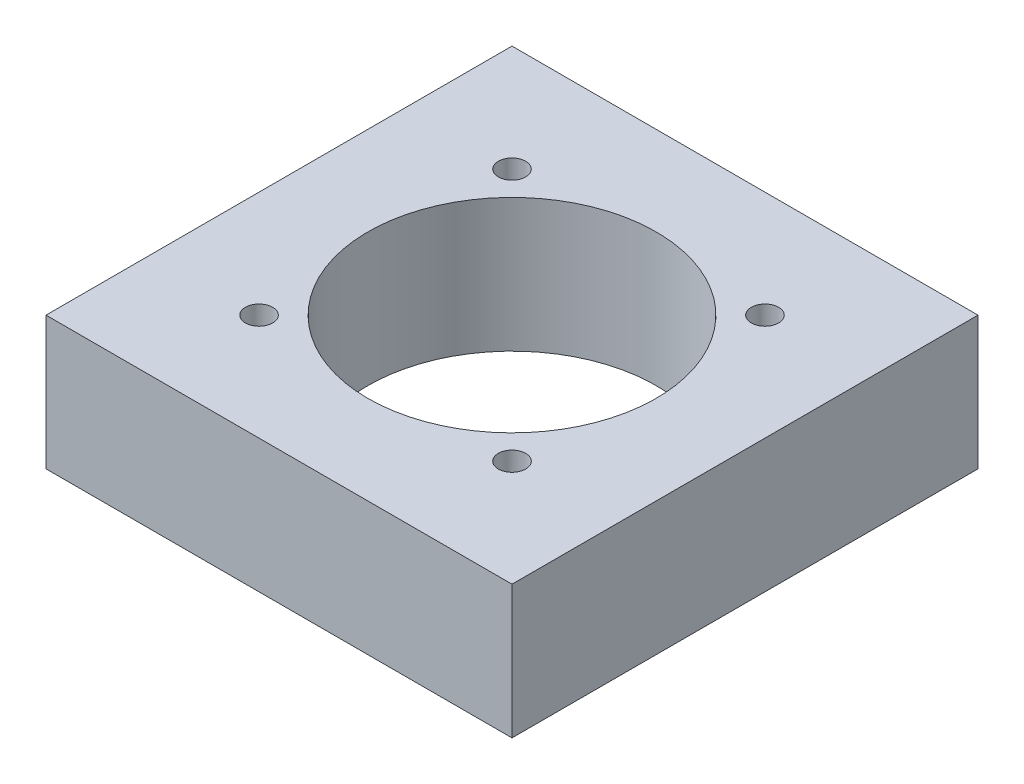
SolidWorks part; units mm, degrees
ref_plane "Front" through (0, 0, 0) normal (0, 0, 1) x (1, 0, 0)
ref_plane "Top" through (0, 0, 0) normal (0, 1, 0) x (1, 0, 0)
ref_plane "Right" through (0, 0, 0) normal (1, 0, 0) x (0, 0, -1)
sketch "Sketch2" plane through (0, 0, 0) normal (0, 1, 0) x (1, 0, 0)
  line L1 (-35, -35) -> (35, -35)
  line L2 (-35, -35) -> (-35, 35)
  line L3 (-35, 35) -> (35, 35)
  line L4 (35, -35) -> (35, 35)
  line L5 (-35, -35) -> (35, 35) construction
  line L6 (-35, 35) -> (35, -35) construction
  point P0 (0, 0)
  dimension "D1" = 70
extrude "Boss-Extrude1" add sketch "Sketch2" against normal blind 20
sketch "Sketch1" plane through (0, 0, 0) normal (0, 0, 1) x (1, 0, 0)
  line L0 (0, 0) -> (0, -14) construction
  line L1 (-15, 0) -> (15, 0) construction
  line L2 (-15, 0) -> (-15, -9) construction
  line L3 (-15, -9) -> (15, -9) construction
  line L4 (15, 0) -> (15, -9) construction
  line L5 (0, 0) -> (18, 0) construction
  line L6 (18, 0) -> (15.6756, -14.676) construction
  line L7 (-15, -20) -> (15, -20) construction
  line L8 (-15, -17) -> (15, -17) construction
  line L9 (-15, -14) -> (15, -14) construction
  line L10 (18, 0) -> (18, 4) construction
  line L11 (18, 4) -> (0, 4) construction
  line L12 (0, 4) -> (0, 0) construction
  line L13 (0, -17.2) -> (0, 0)
  line L14 (0, 0) -> (21.2417, 0)
  line L15 (-35, 0) -> (35, 0) construction
  line L16 (21.2417, 0) -> (21.1589, -0.5115)
  spline S0 degree 3 poles (0, -14) (16.3895, -14) (17.0195, -6.0548) (18, 0) knots 0 0 0 0 1 1 1 1 construction
  spline S1 degree 1 poles (0, -17.2) (21.1589, -0.5115) knots 0 0 1 1 construction
  spline S2 degree 3 poles (0, -17.2) (0.5307, -17.2) (1.6116, -17.1835) (3.6155, -17.0859) (5.9441, -16.8449) (8.4484, -16.3701) (11.4427, -15.4929) (14.5797, -13.9372) (17.3822, -11.4027) (19.199, -8.5009) (20.2357, -5.5832) (20.7065, -3.3134) (20.9819, -1.6359) (21.0969, -0.8942) (21.1589, -0.5115) knots 0 0 0 0 0.03125 0.0625 0.125 0.1875 0.25 0.375 0.5 0.625 0.75 0.875 0.9375 1 1 1 1
  dimension "D1" = 30
  dimension "D2" = 9
  dimension "D3" = 18
  dimension "D4" = 20
  dimension "D5" = 3
  dimension "D6" = 3
  dimension "D7" = 81
  dimension "D8" = 18
  dimension "D9" = 3.2
revolve "Cut-Revolve1" cut sketch "Sketch1" angle 360 about L13
sketch "Sketch3" plane through (0, 0, 0) normal (0, 1, 0) x (1, 0, 0)
  line L0 (-32.7416, 0) -> (25.0655, 0) construction
  line L1 (-19, -19) -> (19, -19) construction
  line L2 (-19, -19) -> (-19, 19) construction
  line L3 (-19, 19) -> (19, 19) construction
  line L4 (19, -19) -> (19, 19) construction
  line L5 (-19, -19) -> (19, 19) construction
  line L6 (-19, 19) -> (19, -19) construction
  circle A0 centre (-19, 19) radius 2.05
  circle A1 centre (19, -19) radius 2.05
  circle A2 centre (-19, -19) radius 2.05
  circle A3 centre (19, 19) radius 2.05
  point P0 (0, 0)
  dimension "D2" = 4.1
  dimension "D1" = 38
extrude "Cut-Extrude1" cut sketch "Sketch3" against normal blind 5
sketch "Sketch4" plane through (0, 0, 0) normal (0, 1, 0) x (1, 0, 0)
  line L0 (-21.6589, 12.1774) -> (-21.6589, -14.0727) construction
  line L1 (-21.1589, 13.8832) -> (-21.1589, -14.0727) construction
  circle A0 centre (0, 0) radius 21.6589
  circle A1 centre (0, 0) radius 21.1589 construction
  dimension "D1" = 0.5
extrude "Cut-Extrude2" cut sketch "Sketch4" against normal through all
